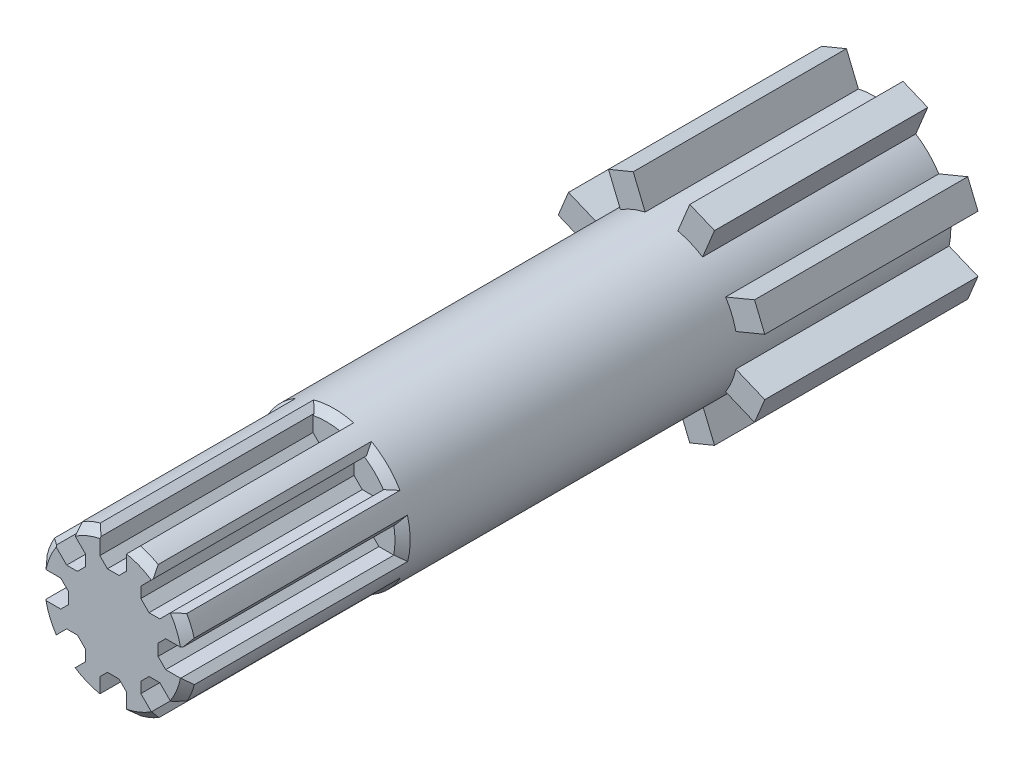
SolidWorks part; units mm, degrees
ref_plane "Front Plane" through (0, 0, 0) normal (0, 0, 1) x (1, 0, 0)
ref_plane "Top Plane" through (0, 0, 0) normal (0, 1, 0) x (1, 0, 0)
ref_plane "Right Plane" through (0, 0, 0) normal (1, 0, 0) x (0, 0, -1)
sketch "Sketch2" plane through (0, 0, 0) normal (0, 0, 1) x (1, 0, 0)
  line L0 (1.7413, 3.054) -> (1.129, 1.5758)
  line L1 (1.7413, 3.054) -> (0.9283, 3.3908)
  line L2 (1.129, 1.5758) -> (0.316, 1.9126)
  line L4 (0.9283, 3.3908) -> (0.316, 1.9126)
  line L5 (3.3908, 0.9283) -> (1.9126, 0.316)
  line L6 (0, 0) -> (2.3775, 5.7398) construction
  line L8 (3.3908, 0.9283) -> (3.054, 1.7413)
  line L9 (1.9126, 0.316) -> (1.5758, 1.129)
  line L10 (3.054, 1.7413) -> (1.5758, 1.129)
  line L11 (3.054, -1.7413) -> (1.5758, -1.129)
  line L12 (3.054, -1.7413) -> (3.3908, -0.9283)
  line L13 (1.5758, -1.129) -> (1.9126, -0.316)
  line L14 (3.3908, -0.9283) -> (1.9126, -0.316)
  line L15 (0.9283, -3.3908) -> (0.316, -1.9126)
  line L16 (0.9283, -3.3908) -> (1.7413, -3.054)
  line L17 (0.316, -1.9126) -> (1.129, -1.5758)
  line L18 (1.7413, -3.054) -> (1.129, -1.5758)
  line L19 (-1.7413, -3.054) -> (-1.129, -1.5758)
  line L20 (-1.7413, -3.054) -> (-0.9283, -3.3908)
  line L21 (-1.129, -1.5758) -> (-0.316, -1.9126)
  line L22 (-0.9283, -3.3908) -> (-0.316, -1.9126)
  line L23 (-3.3908, -0.9283) -> (-1.9126, -0.316)
  line L24 (-3.3908, -0.9283) -> (-3.054, -1.7413)
  line L25 (-1.9126, -0.316) -> (-1.5758, -1.129)
  line L26 (-3.054, -1.7413) -> (-1.5758, -1.129)
  line L27 (-3.054, 1.7413) -> (-1.5758, 1.129)
  line L28 (-3.054, 1.7413) -> (-3.3908, 0.9283)
  line L29 (-1.5758, 1.129) -> (-1.9126, 0.316)
  line L30 (-3.3908, 0.9283) -> (-1.9126, 0.316)
  line L31 (-0.9283, 3.3908) -> (-0.316, 1.9126)
  line L32 (-0.9283, 3.3908) -> (-1.7413, 3.054)
  line L33 (-0.316, 1.9126) -> (-1.129, 1.5758)
  line L34 (-1.7413, 3.054) -> (-1.129, 1.5758)
  point P12 (0.7225, 1.7442)
  point P42 (0, 0)
  dimension "D1" = 0.88
  dimension "D3" = 1.6
  dimension "D4" = 8
sketch "Sketch3" plane through (0, 0, 0) normal (0, 0, 1) x (1, 0, 0)
  circle A0 centre (0, 0) radius 2.5
  dimension "D1" = 5
extrude "Boss-Extrude1" add sketch "Sketch3" along normal blind 25
extrude "Boss-Extrude2" add sketch "Sketch2" along normal blind 7
sketch "Sketch4" plane through (0, 0, 25) normal (0, 0, 1) x (1, 0, 0)
  line L0 (1.3519, 0.7296) -> (2.0513, 1.429)
  line L1 (0.7296, 1.3519) -> (1.3519, 0.7296)
  line L2 (1.429, 2.0513) -> (0.7296, 1.3519)
  line L3 (1.4719, -0.44) -> (2.461, -0.44)
  line L8 (0.44, 1.4719) -> (0.44, 2.461)
  line L9 (-0.44, 1.4719) -> (0.44, 1.4719)
  line L10 (-0.44, 2.461) -> (-0.44, 1.4719)
  line L12 (1.4719, 0.44) -> (1.4719, -0.44)
  line L13 (2.461, 0.44) -> (1.4719, 0.44)
  line L14 (0.7296, -1.3519) -> (1.429, -2.0513)
  line L15 (1.3519, -0.7296) -> (0.7296, -1.3519)
  line L20 (2.0513, -1.429) -> (1.3519, -0.7296)
  line L21 (-0.44, -1.4719) -> (-0.44, -2.461)
  line L22 (0.44, -1.4719) -> (-0.44, -1.4719)
  line L23 (0.44, -2.461) -> (0.44, -1.4719)
  line L28 (-1.3519, -0.7296) -> (-2.0513, -1.429)
  line L29 (-0.7296, -1.3519) -> (-1.3519, -0.7296)
  line L30 (-1.429, -2.0513) -> (-0.7296, -1.3519)
  line L31 (-1.4719, 0.44) -> (-2.461, 0.44)
  line L36 (-1.4719, -0.44) -> (-1.4719, 0.44)
  line L37 (-2.461, -0.44) -> (-1.4719, -0.44)
  line L38 (-0.7296, 1.3519) -> (-1.429, 2.0513)
  line L39 (-1.3519, 0.7296) -> (-0.7296, 1.3519)
  line L44 (-2.0513, 1.429) -> (-1.3519, 0.7296)
  arc A0 (2.0513, 1.429) -> (1.429, 2.0513) centre (0, 0) ccw
  arc A2 (0.44, 2.461) -> (-0.44, 2.461) centre (0, 0) ccw
  arc A10 (2.461, -0.44) -> (2.461, 0.44) centre (0, 0) ccw
  arc A11 (1.429, -2.0513) -> (2.0513, -1.429) centre (0, 0) ccw
  arc A12 (-0.44, -2.461) -> (0.44, -2.461) centre (0, 0) ccw
  arc A13 (-2.0513, -1.429) -> (-1.429, -2.0513) centre (0, 0) ccw
  arc A14 (-2.461, 0.44) -> (-2.461, -0.44) centre (0, 0) ccw
  arc A15 (-1.429, 2.0513) -> (-2.0513, 1.429) centre (0, 0) ccw
  point P37 (0, 0)
  dimension "D2" = 8
extrude "Cut-Extrude1" cut sketch "Sketch4" against normal blind 7
chamfer "Chamfer1" distance 0.25 angle 45 16 edges at (-1.4719, -0.44, 21.5) (-1.4719, 0.44, 21.5) (-1.3519, -0.7296, 21.5) (-0.7296, -1.3519, 21.5) (0.44, -1.4719, 21.5) (1.3519, -0.7296, 21.5) (-0.44, -1.4719, 21.5) (0.7296, -1.3519, 21.5) (1.4719, 0.44, 21.5) (1.4719, -0.44, 21.5) (0.7296, 1.3519, 21.5) (1.3519, 0.7296, 21.5) (0.44, 1.4719, 21.5) (-0.44, 1.4719, 21.5) (-1.3519, 0.7296, 21.5) (-0.7296, 1.3519, 21.5)
chamfer "Chamfer2" distance 0.25 angle 45 32 edges at (-2.461, 0.44, 21.5) (-2.5, 0, 18) (-2.461, -0.44, 21.5) (-2.3097, -0.9567, 25) (-2.0513, -1.429, 21.5) (-1.7678, -1.7678, 18) (-1.429, -2.0513, 21.5) (-0.9567, -2.3097, 25) (-0.44, -2.461, 21.5) (0, -2.5, 18) (0.44, -2.461, 21.5) (0.9567, -2.3097, 25) (1.429, -2.0513, 21.5) (1.7678, -1.7678, 18) (2.0513, -1.429, 21.5) (2.3097, -0.9567, 25) (2.461, -0.44, 21.5) (2.5, 0, 18) (2.461, 0.44, 21.5) (2.3097, 0.9567, 25) (2.0513, 1.429, 21.5) (1.7678, 1.7678, 18) (1.429, 2.0513, 21.5) (0.9567, 2.3097, 25) (0.44, 2.461, 21.5) (0, 2.5, 18) (-0.44, 2.461, 21.5) (-0.9567, 2.3097, 25) (-1.429, 2.0513, 21.5) (-1.7678, 1.7678, 18) (-2.0513, 1.429, 21.5) (-2.3097, 0.9567, 25)
